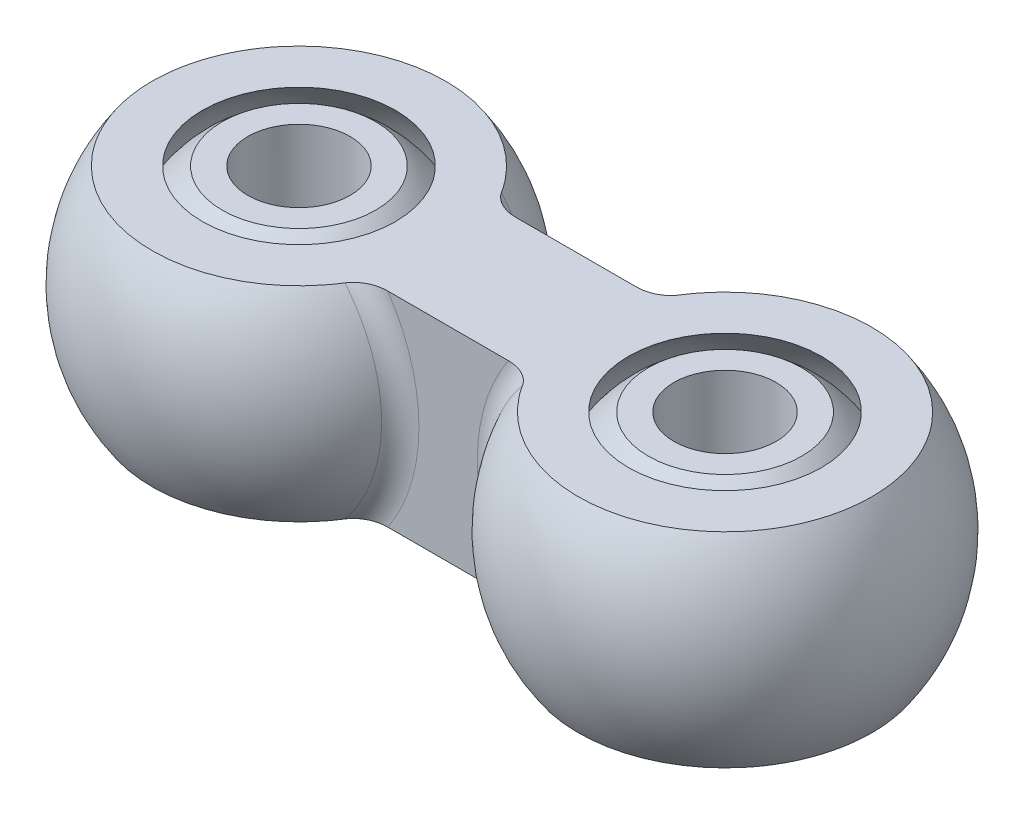
SolidWorks part; units mm, degrees
ref_plane "Alzado" through (0, 0, 0) normal (0, 0, 1) x (1, 0, 0)
ref_plane "Planta" through (0, 0, 0) normal (0, 1, 0) x (1, 0, 0)
ref_plane "Vista lateral" through (0, 0, 0) normal (1, 0, 0) x (0, 0, -1)
sketch "Croquis1" plane through (0, 0, 0) normal (0, 0, 1) x (1, 0, 0)
  line L0 (-8.335, 0) -> (8.335, 0) construction
  line L1 (-8.335, 0) -> (-8.335, 5) construction
  line L2 (-8.335, 5) -> (-8.335, 5.5) construction
  line L3 (-8.335, 5.5) -> (-8.335, 7) construction
  line L4 (-13.335, 0) -> (-3.335, 0)
  line L5 (-13.835, 0) -> (-15.335, 0)
  line L6 (-2.835, 0) -> (-1.335, 0)
  line L7 (0, 0) -> (0, 4.3206) construction
  line L8 (2.835, 0) -> (1.335, 0)
  line L9 (13.835, 0) -> (15.335, 0)
  line L10 (13.335, 0) -> (3.335, 0)
  arc A0 (-3.335, 0) -> (-13.335, 0) centre (-8.335, 0) ccw
  arc A1 (-2.835, 0) -> (-13.835, 0) centre (-8.335, 0) ccw
  arc A2 (-1.335, 0) -> (-15.335, 0) centre (-8.335, 0) ccw
  arc A3 (2.835, 0) -> (13.835, 0) centre (8.335, 0) cw
  arc A4 (1.335, 0) -> (15.335, 0) centre (8.335, 0) cw
  arc A5 (3.335, 0) -> (13.335, 0) centre (8.335, 0) cw
  point P4 (0, 0)
  dimension "D1" = 16.67
  dimension "D2" = 5
  dimension "D3" = 0.5
  dimension "D4" = 1.5
revolve "Revolución1" add sketch "Croquis1" angle 360 about L0
sketch "Croquis2" plane through (0, 0, 0) normal (0, 0, 1) x (1, 0, 0)
  line L0 (0, 0) -> (-1.407, 0) construction
  line L1 (0, 0) -> (0, 4) construction
  line L2 (0, 4) -> (-15, 4)
  line L3 (-15, 4) -> (-15, 9)
  line L4 (-15, 9) -> (15, 9)
  line L5 (15, 9) -> (15, 4)
  line L6 (15, 4) -> (0, 4)
  line L7 (15, -9) -> (15, -4)
  line L8 (-15, -9) -> (15, -9)
  line L9 (-15, -4) -> (-15, -9)
  line L10 (0, -4) -> (-15, -4)
  line L11 (15, -4) -> (0, -4)
  dimension "D1" = 4
  dimension "D2" = 5
  dimension "D3" = 30
extrude "Cortar-Extruir1" cut sketch "Croquis2" against normal mid plane 20
sketch "Croquis3" plane through (0, 0, 0) normal (1, 0, 0) x (0, 0, -1)
  line L0 (-2.5, 4) -> (-2.5, -4)
  line L2 (-2.5, -4) -> (2.5, -4)
  line L3 (2.5, -4) -> (2.5, 4)
  line L4 (2.5, 4) -> (-2.5, 4)
  point P11 (0, 4)
  dimension "D1" = 8
  dimension "D2" = 5
extrude "Saliente-Extruir1" add sketch "Croquis3" along normal up to surface and the other way up to surface up to face at (2.5904, -4, 0) other way up to face at (-14.0796, -4, 0)
sketch "Croquis4" plane through (0, 0, 0) normal (0, 1, 0) x (1, 0, 0)
  circle A0 centre (-8.335, 0) radius 2
  circle A1 centre (8.335, 0) radius 2
  dimension "D1" = 4
extrude "Cortar-Extruir3" cut sketch "Croquis4" against normal mid plane 10
fillet "Redondeo1" radius 1 4 edges at (1.7967, 0, -2.5) (-1.7967, 0, -2.5) (1.7967, 0, 2.5) (-1.7967, 0, 2.5)
